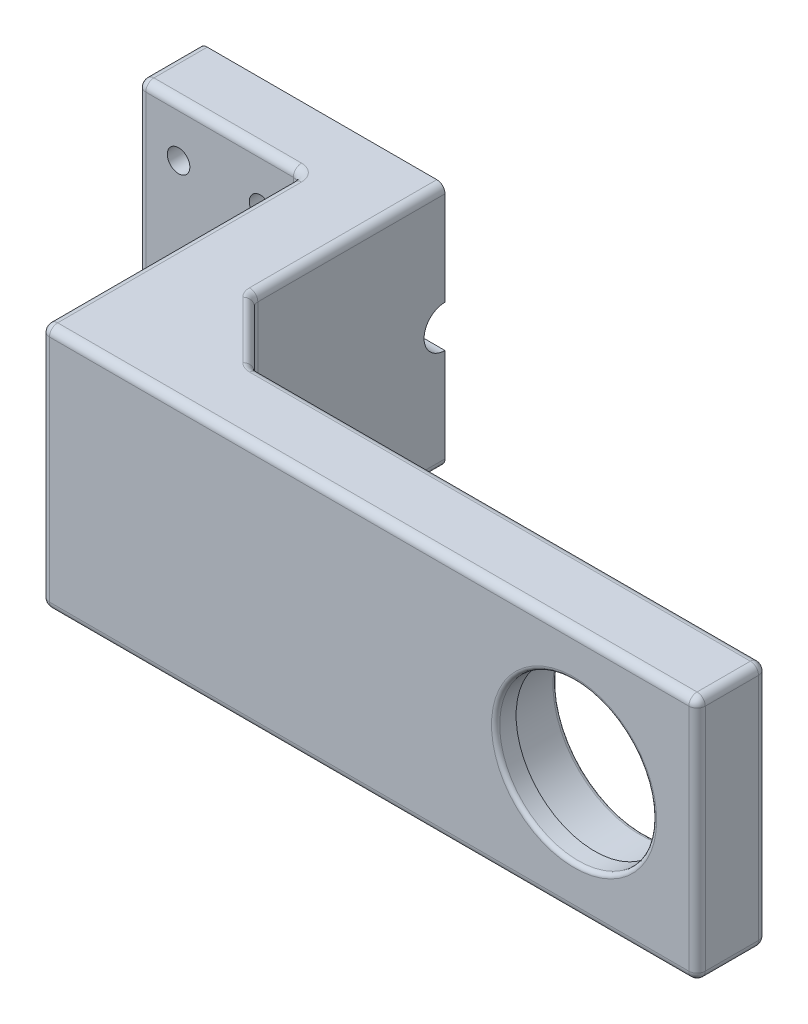
SolidWorks part; units mm, degrees
ref_plane "Front Plane" through (0, 0, 0) normal (0, 0, 1) x (1, 0, 0)
ref_plane "Top Plane" through (0, 0, 0) normal (0, 1, 0) x (1, 0, 0)
ref_plane "Right Plane" through (0, 0, 0) normal (1, 0, 0) x (0, 0, -1)
sketch "Sketch1" plane through (0, 0, 0) normal (0, 0, 1) x (1, 0, 0)
  line L0 (-43.359, 0) -> (46.4553, 0) construction
  line L2 (-30, 30) -> (30, 30)
  line L3 (-30, 30) -> (-30, -30)
  line L4 (-30, -30) -> (30, -30)
  line L5 (30, 30) -> (30, -30)
  line L6 (-30, 30) -> (30, -30) construction
  line L7 (-30, -30) -> (30, 30) construction
  circle A0 centre (0, 0) radius 21.15
  point P3 (0, 0)
  dimension "D1" = 42.3
  dimension "D2" = 60
  dimension "D3" = 60
extrude "Boss-Extrude1" add sketch "Sketch1" along normal blind 12
sketch "Sketch2" plane through (0, 0, 12) normal (0, 0, 1) x (1, 0, 0)
  line L0 (-30, 30) -> (-30, -30) construction
  line L1 (30, 30) -> (-30, 30) construction
  line L2 (-30, 30) -> (-30, -30)
  line L3 (30, 30) -> (-30, 30)
  line L4 (-30, -30) -> (30, -30) construction
  line L5 (30, -30) -> (30, 30) construction
  line L6 (-30, -30) -> (30, -30)
  line L7 (30, -30) -> (30, 30)
  circle A2 centre (0, 0) radius 19.15
  circle A3 centre (0, 0) radius 19.15
  dimension "D1" = 2
extrude "Boss-Extrude2" add sketch "Sketch2" along normal blind 5
sketch "Sketch3" plane through (0, 0, 0) normal (0, 1, 0) x (1, 0, 0)
  line L0 (0, -8.5) -> (-185.6203, -8.5) construction
  line L1 (-30, 0) -> (-110, 0)
  line L2 (-110, 0) -> (-110, 61.5)
  line L3 (-120, -8.5) -> (-120, 96.7953) construction
  line L4 (0, 0) -> (0, -17) construction
  line L5 (30, -17) -> (-30, -17) construction
  line L6 (-30, -17) -> (-130, -17)
  line L7 (-130, -17) -> (-130, 61.5)
  line L8 (-130, 61.5) -> (-110, 61.5)
  line L9 (-30, 0) -> (-30, -17)
  dimension "D1" = 120
  dimension "D2" = 10
  dimension "D3" = 10
  dimension "D4" = 70
extrude "Boss-Extrude3" add sketch "Sketch3" along normal mid plane 60
sketch "Sketch4" plane through (-130, 0, 0) normal (-1, 0, 0) x (0, 0, 1)
  line L0 (-61.5, -30) -> (17, -30) construction
  line L1 (-61.5, 30) -> (-46.5, 30)
  line L2 (-61.5, 30) -> (-61.5, -30)
  line L3 (-61.5, -30) -> (-46.5, -30)
  line L4 (-46.5, 30) -> (-46.5, -30)
  dimension "D1" = 15
extrude "Boss-Extrude4" add sketch "Sketch4" along normal blind 40
sketch "Sketch5" plane through (-170, 0, 0) normal (-1, 0, 0) x (0, 0, 1)
  line L0 (-46.5, 0) -> (-61.5, 0) construction
  line L1 (-46.5, -30) -> (-46.5, 30) construction
  line L2 (-61.5, 30) -> (-61.5, -30) construction
  circle A0 centre (-61.5, 0) radius 5.1
  dimension "D1" = 10.2
extrude "Cut-Extrude1" cut sketch "Sketch5" against normal through all and the other way through all
sketch "Sketch6" plane through (0, 0, -46.5) normal (0, 0, 1) x (1, 0, 0)
  line L0 (-140, 30) -> (-140, -30) construction
  line L1 (-170, 30) -> (-130, 30) construction
  line L2 (-170, -30) -> (-130, -30) construction
  line L3 (-170, 0) -> (-130, 0) construction
  line L4 (-170, -30) -> (-170, 30) construction
  line L5 (-130, 30) -> (-130, -30) construction
  line L6 (-150, 30) -> (-150, -30) construction
  circle A0 centre (-140, 17.5) radius 2.75
  circle A1 centre (-140, -17.5) radius 2.75
  circle A2 centre (-160, -17.5) radius 2.75
  circle A3 centre (-160, 17.5) radius 2.75
  dimension "D1" = 5.5
  dimension "D2" = 20
  dimension "D3" = 35
extrude "Cut-Extrude2" cut sketch "Sketch6" against normal through all
chamfer "Chamfer1" distance 15 angle 45 1 edges at (-110, 0, 0)
fillet "Fillet1" radius 1 1 edges at (21.15, 0, 0)
fillet "Fillet2" radius 1 1 edges at (19.15, 0, 17)
fillet "Fillet3" radius 2 23 edges at (-150, 30, -46.5) (-150, -30, -46.5) (-102.5, 30, -7.5) (-102.5, -30, -7.5) (-130, 30, -14.75) (-130, -30, -14.75) (-130, 0, -46.5) (30, 0, 17) (-50, -30, 17) (-130, 0, 17) (-50, 30, 17) (-110, -30, -38.25) (-110, 0, -15) (-110, 30, -38.25) (30, 0, 0) (-32.5, 30, 0) (-95, 0, 0) (-32.5, -30, 0) (30, -30, 8.5) (30, 30, 8.5) (-170, -30, -54) (-170, 30, -54) (-170, 0, -46.5)
